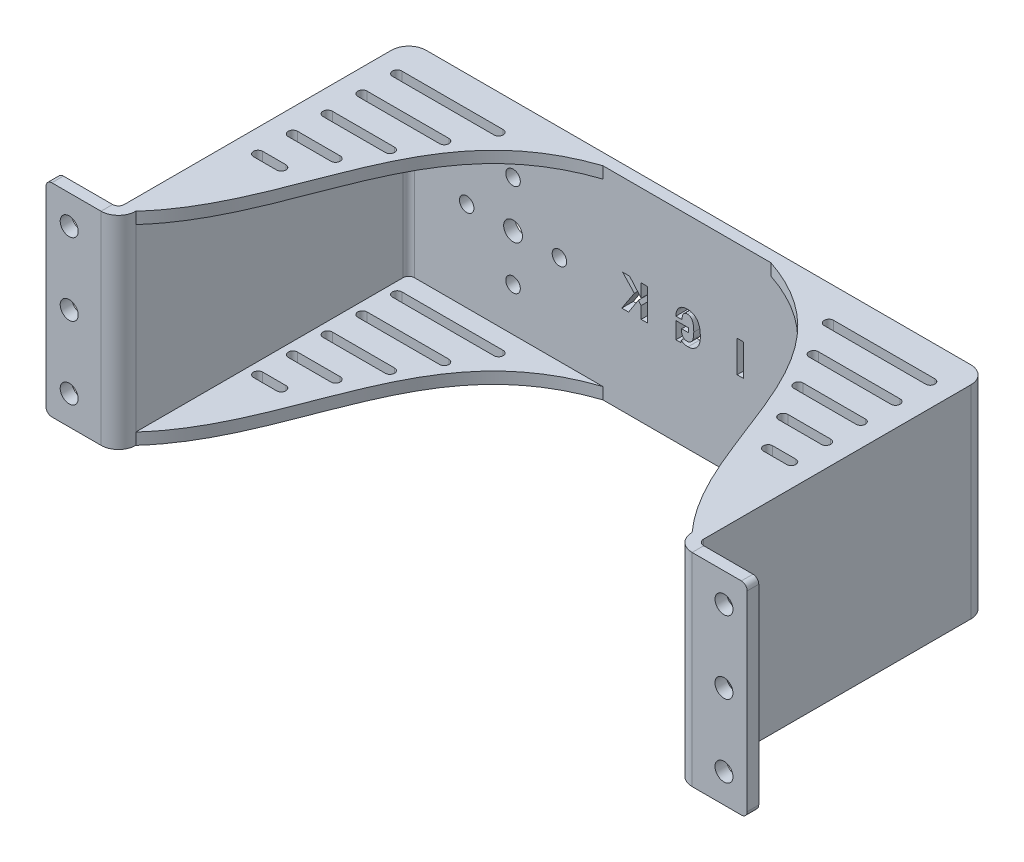
SolidWorks part; units mm, degrees
note: The reader was unsure of these and kept them because the rebuilt part matched: thickness of "基体-法兰1", "边线-法兰1", "边线-法兰2", "钣金6", "钣金7", "钣金8", "钣金9", "钣金10", "钣金11", "钣金12", "钣金13", "钣金14", "钣金15"; flange length of "边线-法兰1", "边线-法兰2".
ref_plane "前视基准面" through (0, 0, 0) normal (0, 0, 1) x (1, 0, 0)
ref_plane "上视基准面" through (0, 0, 0) normal (0, 1, 0) x (1, 0, 0)
ref_plane "右视基准面" through (0, 0, 0) normal (1, 0, 0) x (0, 0, -1)
sketch "草图1" plane through (0, 0, 0) normal (0, 0, 1) x (1, 0, 0)
  line L1 (-100, 35) -> (100, 35)
  line L2 (-100, 35) -> (-100, -35)
  line L3 (-100, -35) -> (100, -35)
  line L4 (100, 35) -> (100, -35)
  line L5 (-100, 35) -> (100, -35) construction
  line L6 (-100, -35) -> (100, 35) construction
  point P0 (0, 0)
  dimension "D1" = 200
  dimension "D2" = 70
base flange "基体-法兰1" sketch "草图1" thickness 4 reverse thickness direction no parameters "D1"=2
edge flange "边线-法兰1" sketch "草图13" flange profiles "草图13", "草图14" flange angle 90 flange length 104.2 flange position material inside bend radius 2 thickness 4 relief rectangular parameters "D6"=10, "D8"=1
sketch "草图13" plane through (-100, 0, 0) normal (-1, 0, 0) x (0, -1, 0)
  line L2 (-35, 0) -> (-35, 100.2)
  line L3 (-35, 100.2) -> (35, 100.2)
  line L4 (35, 100.2) -> (35, 0)
  line L7 (-35, 0) -> (35, 0) construction
  line L8 (-35, 0) -> (35, 0)
sketch "草图14" plane through (100, 0, 0) normal (1, 0, 0) x (0, 1, 0)
  line L0 (-35, 0) -> (35, 0) construction
  line L1 (-35, 0) -> (35, 0)
  line L2 (-35, 0) -> (-35, 100.2)
  line L3 (-35, 100.2) -> (35, 100.2)
  line L4 (35, 100.2) -> (35, 0)
bend "边线折弯1" bend radius 2 bend angle 90 parameters "D5"=1
bend "边线折弯2" bend radius 2 bend angle 90 parameters "D5"=2
edge flange "边线-法兰2" sketch "草图19" flange profiles "草图19", "草图20" flange angle 90 flange length 25 flange position material inside bend radius 2 thickness 4 relief rectangular parameters "D6"=10, "D8"=1
sketch "草图19" plane through (-100, 0, 100.2) normal (0, 0, 1) x (0, 1, 0)
  line L2 (-35, 0) -> (-35, 21)
  line L3 (-35, 21) -> (35, 21)
  line L4 (35, 21) -> (35, 0)
  line L7 (-35, 0) -> (35, 0) construction
  line L8 (-35, 0) -> (35, 0)
sketch "草图20" plane through (100, 0, 100.2) normal (0, 0, 1) x (0, -1, 0)
  line L0 (-35, 0) -> (35, 0) construction
  line L1 (-35, 0) -> (35, 0)
  line L2 (-35, 0) -> (-35, 21)
  line L3 (-35, 21) -> (35, 21)
  line L4 (35, 21) -> (35, 0)
bend "边线折弯3" bend radius 2 bend angle 90 parameters "D5"=3
bend "边线折弯4" bend radius 2 bend angle 90 parameters "D5"=4
sketch "草图21" plane through (0, 0, -4) normal (0, 0, -1) x (-1, 0, 0)
  line L0 (0, 0) -> (-149.1098, 0) construction
  line L3 (0, -35) -> (0, 35) construction
  line L4 (94, -35) -> (-94, -35) construction
  line L5 (-94, 35) -> (94, 35) construction
  circle A1 centre (-60, 0) radius 3.25
  circle A2 centre (60, 0) radius 3.25
  circle A3 centre (-60, 0) radius 16 construction
  circle A4 centre (-60, -16) radius 2.5
  circle A5 centre (-76, 0) radius 2.5
  circle A6 centre (-44, 0) radius 2.5
  circle A7 centre (-60, 16) radius 2.5
  circle A8 centre (76, 0) radius 2.5
  circle A9 centre (60, 16) radius 2.5
  circle A10 centre (44, 0) radius 2.5
  circle A11 centre (60, -16) radius 2.5
  point P2 (-60, 0)
  dimension "D1" = 6.5
  dimension "D2" = 60
  dimension "D4" = 32
extrude "切除-拉伸1" cut sketch "草图21" against normal blind 10 normal cut yes
sketch "草图22" plane through (0, 0, 96.2) normal (0, 0, -1) x (-1, 0, 0)
  line L0 (-121, 35) -> (-102, 35) construction
  line L2 (-102, -35) -> (-121, -35) construction
  line L3 (0, 35) -> (0, -42.3342) construction
  line L4 (-94, 35) -> (94, 35) construction
  line L5 (-113, -25) -> (-113, 25) construction
  line L7 (-121, -35) -> (-121, 35) construction
  circle A0 centre (-113, 25) radius 3.1
  circle A1 centre (-113, -25) radius 3.1
  circle A2 centre (113, -25) radius 3.1
  circle A3 centre (113, 25) radius 3.1
  circle A4 centre (-113, 0) radius 3.1
  circle A5 centre (113, 0) radius 3.1
  dimension "D1" = 6.2
  dimension "D2" = 10
  dimension "D3" = 8
  dimension "D4" = 6.2
  dimension "D5" = 10
extrude "切除-拉伸2" cut sketch "草图22" against normal blind 10 normal cut yes
sketch "草图23" plane through (0, 0, -4) normal (0, 0, -1) x (-1, 0, 0)
  line L0 (0, 35) -> (0, -26.2254) construction
  line L1 (-94, 35) -> (94, 35) construction
  line L2 (-100, 0) -> (49.9159, 0) construction
  line L3 (-100, -35) -> (-100, 35) construction
  circle A0 centre (-20, 0) radius 2.6
  circle A1 centre (-20, 14) radius 2.6
  circle A2 centre (-20, -14) radius 2.6
  circle A3 centre (20, -14) radius 2.6
  circle A4 centre (20, 14) radius 2.6
  circle A5 centre (20, 0) radius 2.6
  dimension "D1" = 2
  dimension "D3" = 20
  dimension "D2" = 2
extrude "切除-拉伸3" [suppressed] cut sketch "草图23" against normal blind 10
sketch "草图24" plane through (-100, 0, 0) normal (-1, 0, 0) x (0, 0, 1)
  line L0 (-4, 0) -> (100.2, 0) construction
  line L1 (-4, -35) -> (-4, 35) construction
  line L2 (100.2, 35) -> (100.2, -35) construction
  line L3 (1.7104, 3.1) -> (40.2896, 3.1)
  line L4 (1.7104, -3.1) -> (40.2896, -3.1)
  line L5 (1, -2.3896) -> (1, 2.3896)
  line L6 (41, 2.3896) -> (41, -2.3896)
  arc A0 (40.2896, -3.1) -> (41, -2.3896) centre (40.2896, -2.3896) ccw
  arc A1 (40.2896, 3.1) -> (41, 2.3896) centre (40.2896, 2.3896) cw
  arc A2 (1.7104, 3.1) -> (1, 2.3896) centre (1.7104, 2.3896) ccw
  arc A3 (1, -2.3896) -> (1.7104, -3.1) centre (1.7104, -2.3896) ccw
  point P13 (41, -3.1)
  point P16 (41, 3.1)
  point P19 (1, 3.1)
  point P22 (1, -3.1)
  dimension "D4" = 0.7104
  dimension "D1" = 40
  dimension "D2" = 3.1
  dimension "D3" = 5
extrude "切除-拉伸4" [suppressed] cut sketch "草图24" against normal through all
fillet "圆角1" radius 2 4 edges at (121, 35, 98.2) (121, -35, 98.2) (-121, -35, 98.2) (-121, 35, 98.2)
sketch "草图25" plane through (0, -35, 0) normal (0, -1, 0) x (1, 0, 0)
  line L0 (-100, 94.2) -> (-100, 2)
  line L1 (29, -4) -> (94, -4)
  line L2 (-100, 2) -> (-100, 94.2) construction
  line L3 (-100, 94.2) -> (-96, 94.2)
  line L4 (-96, 2) -> (-96, 94.2) construction
  line L6 (-94, 0) -> (94, 0) construction
  line L7 (-29, 0) -> (-29, -4)
  line L8 (-94, -4) -> (94, -4) construction
  line L9 (-29, -4) -> (-94, -4)
  line L10 (0, -4) -> (0, 129.4667) construction
  line L16 (-100, 94.2) -> (-96, 94.2) construction
  line L17 (29, 0) -> (29, -4)
  line L18 (100, 94.2) -> (96, 94.2)
  line L19 (100, 94.2) -> (100, 2)
  line L20 (-92, 56) -> (-92, 8) construction
  line L23 (-92, 8) -> (-57, 8) construction
  line L26 (-57, 8) -> (-84, 56) construction
  line L29 (-84, 56) -> (-92, 56) construction
  line L32 (-92, 8) -> (-57, 8) construction
  line L35 (-92, 9.6) -> (-57, 9.6)
  line L38 (-92, 6.4) -> (-57, 6.4)
  line L39 (-92, 20) -> (-63.75, 20) construction
  line L40 (-92, 21.6) -> (-63.75, 21.6)
  line L41 (-92, 18.4) -> (-63.75, 18.4)
  line L42 (-92, 32) -> (-70.5, 32) construction
  line L43 (-92, 33.6) -> (-70.5, 33.6)
  line L44 (-92, 30.4) -> (-70.5, 30.4)
  line L45 (-92, 44) -> (-77.25, 44) construction
  line L46 (-92, 45.6) -> (-77.25, 45.6)
  line L47 (-92, 42.4) -> (-77.25, 42.4)
  line L48 (-92, 56) -> (-84, 56) construction
  line L49 (-92, 57.6) -> (-84, 57.6)
  line L50 (-92, 54.4) -> (-84, 54.4)
  line L51 (92, 56) -> (84, 56) construction
  line L52 (92, 57.6) -> (84, 57.6)
  line L53 (92, 54.4) -> (84, 54.4)
  line L54 (92, 44) -> (77.25, 44) construction
  line L55 (92, 45.6) -> (77.25, 45.6)
  line L56 (92, 42.4) -> (77.25, 42.4)
  line L57 (92, 32) -> (70.5, 32) construction
  line L58 (92, 33.6) -> (70.5, 33.6)
  line L59 (92, 30.4) -> (70.5, 30.4)
  line L60 (92, 20) -> (63.75, 20) construction
  line L61 (92, 21.6) -> (63.75, 21.6)
  line L62 (92, 18.4) -> (63.75, 18.4)
  line L63 (92, 8) -> (57, 8) construction
  line L64 (92, 9.6) -> (57, 9.6)
  line L65 (92, 6.4) -> (57, 6.4)
  arc A0 (94, -4) -> (100, 2) centre (94, 2) ccw
  arc A1 (-94, -4) -> (-100, 2) centre (-94, 2) cw
  arc A14 (-92, 9.6) -> (-92, 6.4) centre (-92, 8) ccw
  arc A15 (-57, 6.4) -> (-57, 9.6) centre (-57, 8) ccw
  arc A16 (-92, 21.6) -> (-92, 18.4) centre (-92, 20) ccw
  arc A17 (-63.75, 18.4) -> (-63.75, 21.6) centre (-63.75, 20) ccw
  arc A18 (-92, 33.6) -> (-92, 30.4) centre (-92, 32) ccw
  arc A19 (-70.5, 30.4) -> (-70.5, 33.6) centre (-70.5, 32) ccw
  arc A20 (-92, 45.6) -> (-92, 42.4) centre (-92, 44) ccw
  arc A21 (-77.25, 42.4) -> (-77.25, 45.6) centre (-77.25, 44) ccw
  arc A22 (-92, 57.6) -> (-92, 54.4) centre (-92, 56) ccw
  arc A23 (-84, 54.4) -> (-84, 57.6) centre (-84, 56) ccw
  arc A24 (92, 57.6) -> (92, 54.4) centre (92, 56) cw
  arc A25 (84, 54.4) -> (84, 57.6) centre (84, 56) cw
  arc A26 (92, 45.6) -> (92, 42.4) centre (92, 44) cw
  arc A27 (77.25, 42.4) -> (77.25, 45.6) centre (77.25, 44) cw
  arc A28 (92, 33.6) -> (92, 30.4) centre (92, 32) cw
  arc A29 (70.5, 30.4) -> (70.5, 33.6) centre (70.5, 32) cw
  arc A30 (92, 21.6) -> (92, 18.4) centre (92, 20) cw
  arc A31 (63.75, 18.4) -> (63.75, 21.6) centre (63.75, 20) cw
  arc A32 (92, 9.6) -> (92, 6.4) centre (92, 8) cw
  arc A33 (57, 6.4) -> (57, 9.6) centre (57, 8) cw
  spline S0 degree 3 poles (-96, 94.2) (-69.1449, 64.4541) (-75.0793, 15.4204) (-29, 0) knots 0 0 0 0 1 1 1 1
  spline S1 degree 3 poles (96, 94.2) (69.1449, 64.4541) (75.0793, 15.4204) (29, 0) knots 0 0 0 0 1 1 1 1
  point P34 (-74.5, 8)
  point P40 (-77.875, 20)
  point P47 (-81.25, 32)
  point P54 (-84.625, 44)
  point P61 (-88, 56)
  point P68 (88, 56)
  point P75 (84.625, 44)
  point P82 (81.25, 32)
  point P89 (77.875, 20)
  point P96 (74.5, 8)
  point P101 (-70.8815, 36.1326)
  point P102 (-88, 97.1907)
  point P103 (-67, 35.7071)
  point P104 (-81.25, 78.444)
  point P105 (-81.25, 74.0161)
  point P106 (-81.25, 70.3876)
  dimension "D3" = 6
  dimension "D4" = 1.6
  dimension "D9" = 1.6
  dimension "D10" = 1.6
  dimension "D11" = 1.6
  dimension "D12" = 1.6
  dimension "D1" = 65
  dimension "D2" = 35
  dimension "D5" = 12
  dimension "D6" = 12
  dimension "D7" = 12
  dimension "D8" = 12
  dimension "D13" = 12
  dimension "D14" = 8
  dimension "D15" = 8
extrude "凸台-拉伸1" add sketch "草图25" against normal blind 4
mirror "镜向1" about plane through (0, 0, 0) normal (0, 1, 0) of "凸台-拉伸1"
sketch "草图26" plane through (0, 0, -4) normal (0, 0, -1) x (-1, 0, 0)
  line L0 (22.793, -4.6298) -> (-34.3101, -4.6298) construction
  text T0 "IGK" font "黑体" height in points 36
extrude "切除-拉伸5" cut sketch "草图26" against normal through all normal cut yes
sketch "折弯-线1" plane through (0, 0, 0) normal (0, 1, 0) x (1, 0, 0)
sketch "边界框1" plane through (0, 0, 0) normal (0, 1, 0) x (1, 0, 0)
sheet metal parameters "钣金6" thickness 4 parameters "D1"=2
flat pattern "平板型式6" [suppressed]
sketch "折弯-线2" plane through (0, 0, 0) normal (0, 1, 0) x (1, 0, 0)
sketch "边界框2" [suppressed] plane through (0, 0, 0) normal (0, 1, 0) x (1, 0, 0)
sheet metal parameters "钣金7" thickness 4 parameters "D1"=2, "D7"=3
flat pattern "平板型式6" [suppressed]
sketch "折弯-线2" plane through (0, 0, 0) normal (0, 1, 0) x (1, 0, 0)
sketch "边界框2" [suppressed] plane through (0, 0, 0) normal (0, 1, 0) x (1, 0, 0)
bend of the flat pattern "展平-<边线折弯1>1"
bend of the flat pattern "展平-<边线折弯2>1"
sheet metal parameters "钣金8" thickness 4 parameters "D1"=2, "D7"=3
flat pattern "平板型式6" [suppressed]
sketch "折弯-线2" plane through (0, 0, 0) normal (0, 1, 0) x (1, 0, 0)
sketch "边界框2" [suppressed] plane through (0, 0, 0) normal (0, 1, 0) x (1, 0, 0)
bend of the flat pattern "展平-<边线折弯3>1"
bend of the flat pattern "展平-<边线折弯4>1"
bend of the flat pattern "展平-<边线折弯1>1"
bend of the flat pattern "展平-<边线折弯2>1"
sheet metal parameters "钣金9" thickness 4 parameters "D1"=2, "D7"=3
flat pattern "平板型式6" [suppressed]
sketch "折弯-线2" plane through (0, 0, 0) normal (0, 1, 0) x (1, 0, 0)
sketch "边界框2" [suppressed] plane through (0, 0, 0) normal (0, 1, 0) x (1, 0, 0)
bend of the flat pattern "展平-<边线折弯3>1"
bend of the flat pattern "展平-<边线折弯4>1"
bend of the flat pattern "展平-<边线折弯1>1"
bend of the flat pattern "展平-<边线折弯2>1"
sheet metal parameters "钣金10" thickness 4 parameters "D1"=2, "D7"=3
flat pattern "平板型式6" [suppressed]
sketch "折弯-线2" plane through (0, 0, 0) normal (0, 1, 0) x (1, 0, 0)
sketch "边界框2" [suppressed] plane through (0, 0, 0) normal (0, 1, 0) x (1, 0, 0)
bend of the flat pattern "展平-<边线折弯3>1"
bend of the flat pattern "展平-<边线折弯4>1"
bend of the flat pattern "展平-<边线折弯1>1"
bend of the flat pattern "展平-<边线折弯2>1"
sheet metal parameters "钣金11" thickness 4 parameters "D1"=2, "D7"=3
flat pattern "平板型式6" [suppressed]
sketch "折弯-线2" plane through (0, 0, 0) normal (0, 1, 0) x (1, 0, 0)
sketch "边界框2" [suppressed] plane through (0, 0, 0) normal (0, 1, 0) x (1, 0, 0)
bend of the flat pattern "展平-<边线折弯3>1"
bend of the flat pattern "展平-<边线折弯4>1"
bend of the flat pattern "展平-<边线折弯1>1"
bend of the flat pattern "展平-<边线折弯2>1"
sheet metal parameters "钣金12" thickness 4 parameters "D1"=2, "D7"=3
flat pattern "平板型式6" [suppressed]
sketch "折弯-线2" plane through (0, 0, 0) normal (0, 1, 0) x (1, 0, 0)
sketch "边界框2" [suppressed] plane through (0, 0, 0) normal (0, 1, 0) x (1, 0, 0)
bend of the flat pattern "展平-<边线折弯3>1"
bend of the flat pattern "展平-<边线折弯4>1"
bend of the flat pattern "展平-<边线折弯1>1"
bend of the flat pattern "展平-<边线折弯2>1"
sheet metal parameters "钣金13" thickness 4 parameters "D1"=2, "D7"=3
flat pattern "平板型式6" [suppressed]
sketch "折弯-线2" plane through (0, 0, 0) normal (0, 1, 0) x (1, 0, 0)
sketch "边界框2" [suppressed] plane through (0, 0, 0) normal (0, 1, 0) x (1, 0, 0)
bend of the flat pattern "展平-<边线折弯3>1"
bend of the flat pattern "展平-<边线折弯4>1"
bend of the flat pattern "展平-<边线折弯1>1"
bend of the flat pattern "展平-<边线折弯2>1"
sheet metal parameters "钣金14" thickness 4 parameters "D1"=2, "D7"=3
flat pattern "平板型式6" [suppressed]
sketch "折弯-线2" plane through (0, 0, 0) normal (0, 1, 0) x (1, 0, 0)
sketch "边界框2" [suppressed] plane through (0, 0, 0) normal (0, 1, 0) x (1, 0, 0)
bend of the flat pattern "展平-<边线折弯3>1"
bend of the flat pattern "展平-<边线折弯4>1"
bend of the flat pattern "展平-<边线折弯1>1"
bend of the flat pattern "展平-<边线折弯2>1"
sheet metal parameters "钣金15" thickness 4 parameters "D1"=2, "D7"=3
flat pattern "平板型式6" [suppressed]
sketch "折弯-线2" plane through (0, 0, 0) normal (0, 1, 0) x (1, 0, 0)
sketch "边界框2" [suppressed] plane through (0, 0, 0) normal (0, 1, 0) x (1, 0, 0)
bend of the flat pattern "展平-<边线折弯3>1"
bend of the flat pattern "展平-<边线折弯4>1"
bend of the flat pattern "展平-<边线折弯1>1"
bend of the flat pattern "展平-<边线折弯2>1"
